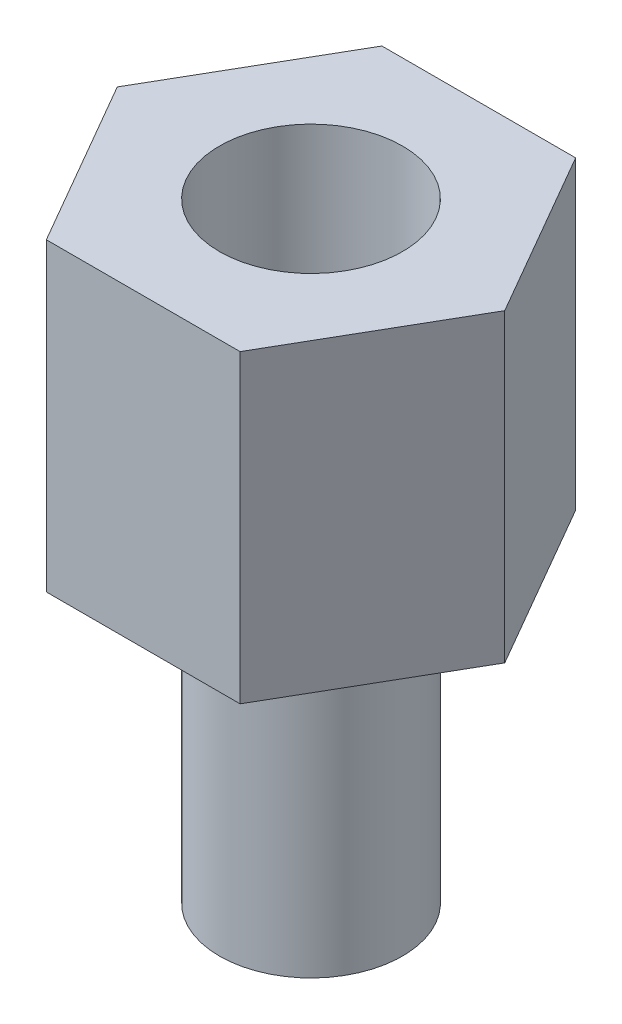
SolidWorks part; units mm, degrees
material "ABS"
ref_plane "Ön Düzlem" through (0, 0, 0) normal (0, 0, 1) x (1, 0, 0)
ref_plane "Üst Düzlem" through (0, 0, 0) normal (0, 1, 0) x (1, 0, 0)
ref_plane "Sağ Düzlem" through (0, 0, 0) normal (1, 0, 0) x (0, 0, -1)
sketch "Çizim1" plane through (0, 0, 0) normal (0, 1, 0) x (1, 0, 0)
  line L1 (1.5877, -2.75) -> (3.1754, 0)
  line L2 (3.1754, 0) -> (1.5877, 2.75)
  line L3 (1.5877, 2.75) -> (-1.5877, 2.75)
  line L4 (-1.5877, 2.75) -> (-3.1754, 0)
  line L5 (-3.1754, 0) -> (-1.5877, -2.75)
  line L6 (-1.5877, -2.75) -> (1.5877, -2.75)
  circle A0 centre (0, 0) radius 1.5
  circle A1 centre (0, 0) radius 2.75 construction
  dimension "D2" = 3
  dimension "D1" = 5.5
extrude "Yükseklik-Ekstrüzyon1" add sketch "Çizim1" along normal blind 5
extrude "Yükseklik-Ekstrüzyon2" add sketch "Çizim1<2>" against normal blind 7 from offset 2 contours A0 region at (0, 0, 0)
sketch "Çizim1<2>" plane through (0, 0, 0) normal (0, 1, 0) x (1, 0, 0) same geometry as "Çizim1"
